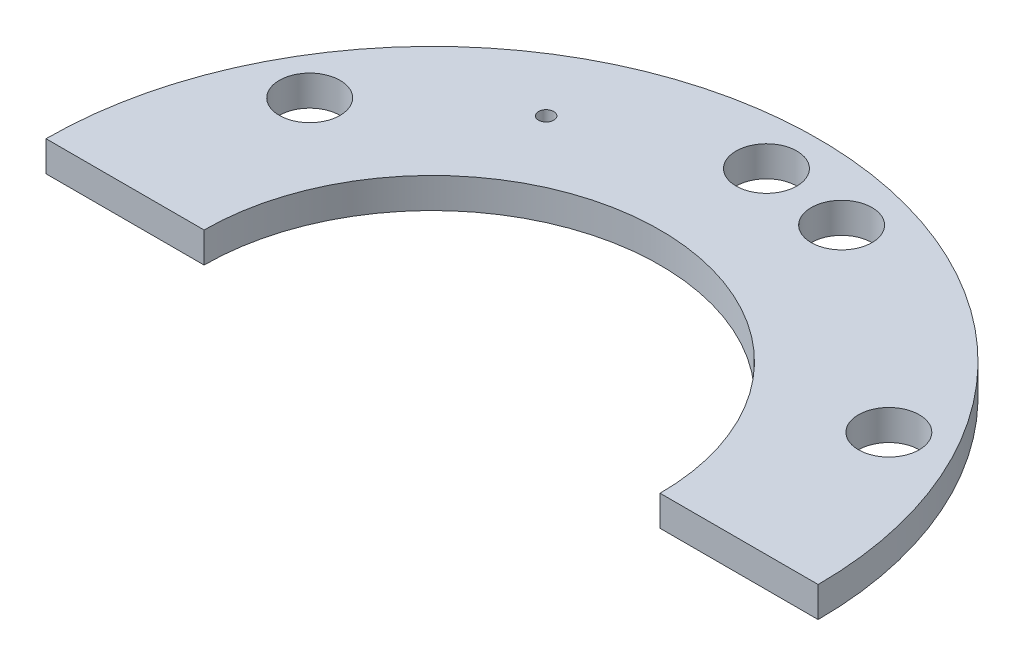
SolidWorks part; units mm, degrees
material "ABS"
ref_plane "Front Plane" through (0, 0, 0) normal (0, 0, 1) x (1, 0, 0)
ref_plane "Top Plane" through (0, 0, 0) normal (0, 1, 0) x (1, 0, 0)
ref_plane "Right Plane" through (0, 0, 0) normal (1, 0, 0) x (0, 0, -1)
sketch "Sketch1" plane through (0, 0, 0) normal (0, 1, 0) x (1, 0, 0)
  circle A0 centre (0, 0) radius 12.7
  dimension "D1" = 25.4
extrude "Boss-Extrude1" add sketch "Sketch1" along normal blind 1
sketch "Sketch19" plane through (0, 1, 0) normal (0, 1, 0) x (1, 0, 0)
  circle A0 centre (0, 11) radius 1
  circle A1 centre (9.5263, 5.5) radius 1
  circle A2 centre (9.5263, -5.5) radius 1
  circle A3 centre (0, -11) radius 1
  circle A4 centre (-9.5263, -5.5) radius 1
  circle A5 centre (-9.5263, 5.5) radius 1
  point P13 (0, 0)
  dimension "D1" = 2
  dimension "D2" = 11
  dimension "D3" = 6
extrude "Cut-Extrude1" cut sketch "Sketch19" against normal through all both and the other way through all
sketch "Sketch20" plane through (0, 1, 0) normal (0, 1, 0) x (1, 0, 0)
  circle A0 centre (0, 0) radius 7.5
  dimension "D1" = 15
extrude "Cut-Extrude2" cut sketch "Sketch20" against normal through all both and the other way through all
sketch "Sketch21" plane through (0, 0, 0) normal (0, 0, 1) x (1, 0, 0)
  line L1 (-36.7533, 32.3113) -> (29.1209, 32.3113)
  line L2 (-36.7533, 32.3113) -> (-36.7533, -19.668)
  line L3 (-36.7533, -19.668) -> (29.1209, -19.668)
  line L4 (29.1209, 32.3113) -> (29.1209, -19.668)
extrude "Cut-Extrude3" cut sketch "Sketch21" along normal through all
sketch "Sketch22" plane through (0, 1, 0) normal (0, 1, 0) x (1, 0, 0)
  line L0 (-5.125, 8.8768) -> (0, 0) construction
  line L1 (0, 0) -> (3.9475, 14.7323) construction
  line L2 (-9.5263, 5.5) -> (0, 11)
  circle A0 centre (-5.125, 8.8768) radius 0.25
  circle A2 centre (2.847, 10.6252) radius 1
  point P14 (-4.7631, 8.25)
  dimension "D1" = 0.5
  dimension "D2" = 10.25
  dimension "D3" = 0
  dimension "D5" = 2
  dimension "D4" = 45
  dimension "D6" = 11
extrude "Cut-Extrude4" cut sketch "Sketch22" against normal through all both and the other way through all contours L2 A0 | L2 A0 | A2 region at (-5.125, 1, -8.8768) region at (2.847, 1, -10.6252)
